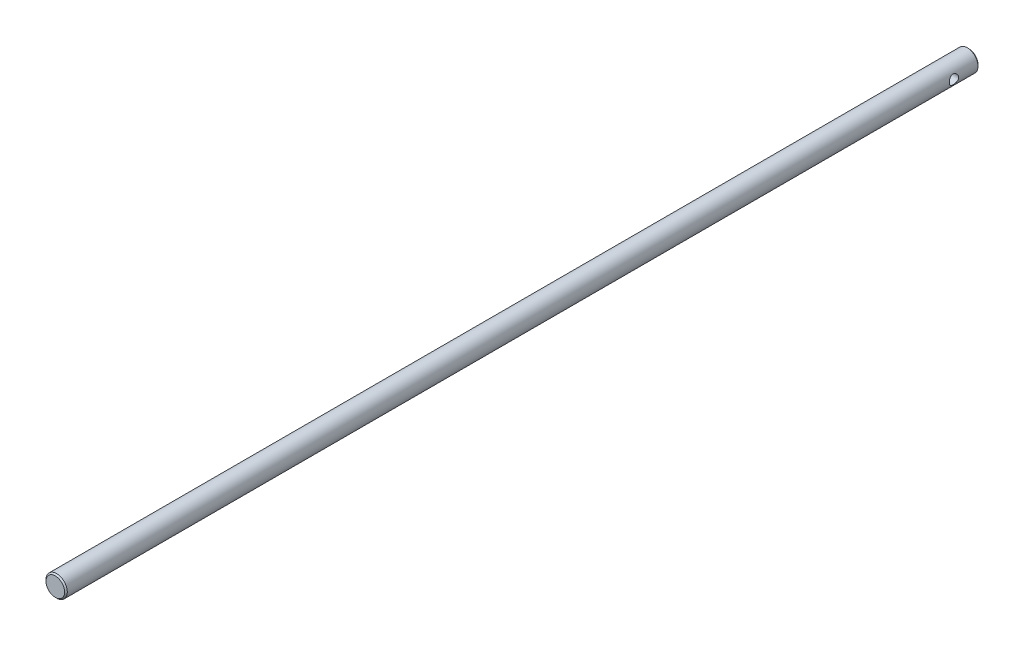
SolidWorks part; units mm, degrees
ref_plane "Front Plane" through (0, 0, 0) normal (0, 0, 1) x (1, 0, 0)
ref_plane "Top Plane" through (0, 0, 0) normal (0, 1, 0) x (1, 0, 0)
ref_plane "Right Plane" through (0, 0, 0) normal (1, 0, 0) x (0, 0, -1)
sketch "Sketch1" plane through (0, 0, 0) normal (0, 0, 1) x (1, 0, 0)
  circle A0 centre (0, 0) radius 4
  dimension "D1" = 8
extrude "Boss-Extrude1" add sketch "Sketch1" along normal blind 342.9
chamfer "Chamfer1" distance 0.5 angle 45 2 edges at (4, 0, 0) (4, 0, 342.9)
sketch "Sketch2" plane through (0, 0, 0) normal (0, 0, -1) x (-1, 0, 0)
  line L0 (-3.5, 0) -> (3.5, 0) construction
  circle A0 centre (0, 0) radius 3.5 construction
ref_plane "Plane1" through (-4, 0, 0) normal (-1, 0, 0) x (0, 0, 1)
sketch "Sketch3" plane through (-4, 0, 0) normal (-1, 0, 0) x (0, 0, 1)
  line L0 (0, 0) -> (342.714, 0) construction
  circle A0 centre (9.525, 0) radius 1.7526
  dimension "D1" = 3.5052
  dimension "D2" = 9.525
extrude "Cut-Extrude1" cut sketch "Sketch3" against normal through all
